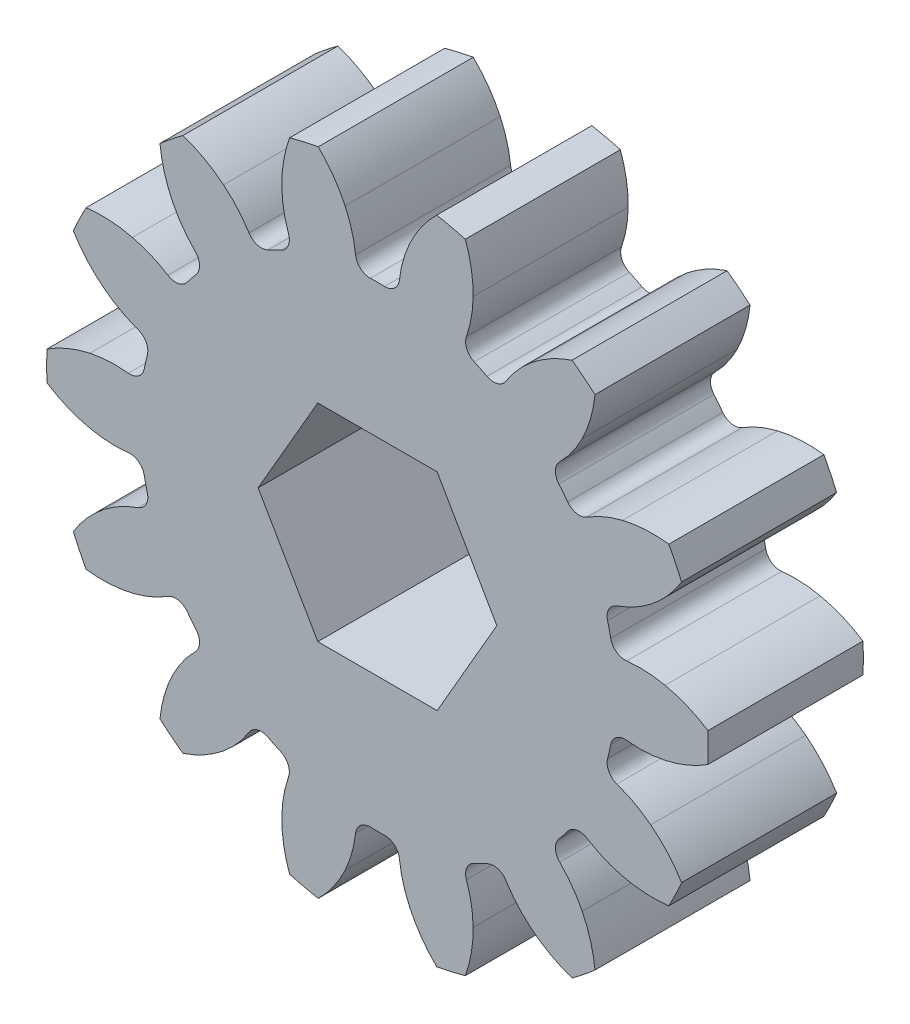
SolidWorks part; units mm, degrees
material "PLA/ABS"
ref_plane "Front" through (0, 0, 0) normal (0, 0, 1) x (1, 0, 0)
ref_plane "Top" through (0, 0, 0) normal (0, 1, 0) x (1, 0, 0)
ref_plane "Right" through (0, 0, 0) normal (1, 0, 0) x (0, 0, -1)
sketch "Sketch1" plane through (0, 0, 0) normal (0, 0, 1) x (1, 0, 0)
  line L0 (0, 0) -> (17.78, 0) construction
  line L1 (17.78, 0) -> (20.32, 0) construction
  circle A0 centre (0, 0) radius 17.78 construction
  circle A1 centre (0, 0) radius 20.32
  dimension "D1" = 35.56
  dimension "D2" = 2.54
extrude "Round Stock" add sketch "Sketch1" along normal mid plane 9.525
sketch "Sketch2" plane through (0, 0, 4.7625) normal (0, 0, 1) x (1, 0, 0)
  line L0 (0, 0) -> (14.605, 0) construction
  line L1 (14.605, 0) -> (17.78, 0) construction
  line L2 (0, 0) -> (-20.32, 0) construction
  line L3 (0, 0) -> (-18.3077, -8.8165) construction
  line L4 (-18.6809, -7.9954) -> (-16.7837, -5.8681) construction
  line L5 (-16.7837, -5.8681) -> (-13.9448, -4.3414) construction
  line L6 (-20.3, -0.9018) -> (-17.6677, -1.9952) construction
  line L7 (-17.6677, -1.9952) -> (-14.4475, -2.139) construction
  line L8 (-15.918, -7.6657) -> (-16.7837, -5.8681) construction
  line L9 (-17.6677, -1.9952) -> (-17.6677, 0) construction
  line L12 (0, 0) -> (-17.6677, -1.9952) construction
  line L13 (0, 0) -> (-16.7837, -5.8681) construction
  line L14 (-16.7837, -5.8681) -> (-13.537, -15.1543) construction
  line L15 (-17.6677, -1.9952) -> (-18.7716, 7.7801) construction
  line L16 (-16.7837, -5.8681) -> (-17.6677, -1.9952) construction
  line L17 (-14.2388, -3.2499) -> (-14.4475, -2.139) construction
  line L18 (-14.2388, -3.2499) -> (-13.9448, -4.3414) construction
  circle A0 centre (0, 0) radius 17.78 construction
  circle A1 centre (0, 0) radius 14.605 construction
  circle A2 centre (0, 0) radius 20.32 construction
  arc A3 (-18.6809, -7.9954) -> (-20.3, -0.9018) centre (0, 0) cw
  arc A4 (-13.9448, -4.3414) -> (-14.4475, -2.139) centre (0, 0) cw construction
  arc A6 (-18.6809, -7.9954) -> (-16.7837, -5.8681) centre (-11.872, -12.1583) cw
  arc A7 (-20.3, -0.9018) -> (-17.6677, -1.9952) centre (-15.9716, 5.8032) ccw
  arc A8 (-16.7837, -5.8681) -> (-14.7048, -4.7372) centre (-12.3428, -11.5554) cw
  arc A9 (-17.6677, -1.9952) -> (-15.304, -2.1121) centre (-16.1342, 5.0557) ccw
  arc A10 (-14.7048, -4.7372) -> (-14.1354, -3.6736) centre (-14.9959, -3.8972) ccw
  arc A11 (-15.304, -2.1121) -> (-14.3295, -2.8233) centre (-15.2017, -2.9952) cw
  arc A12 (-14.1354, -3.6736) -> (-14.3295, -2.8233) centre (0, 0) cw
  dimension "D6" = 35.56
  dimension "D9" = 0.889
  dimension "D12" = 7.9807
  dimension "D2" = 3.175
  dimension "D3" = 25.714
  dimension "D4" = 1.9952
  dimension "D5" = 1.9952
  dimension "D11" = 3.9726
  dimension "D8" = 20
  dimension "D7" = 20
  dimension "D14" = 9
  dimension "D15" = 9
extrude "Single Tooth" cut sketch "Sketch2" against normal through all
ref_axis "Axis" through (0, 0, 50) along (0, 0, -1)
pattern_circular "Tooth Pattern" count 14 over 360 about axis through (0, 0, 50) along (0, 0, -1) of "Single Tooth"
sketch "Sketch4" plane through (0, 0, 4.7625) normal (0, 0, 1) x (1, 0, 0)
  circle A0 centre (0, 0) radius 3.302
  dimension "D1" = 6.604
extrude "TopBearingBoss" [suppressed] add sketch "Sketch4" along normal blind 0.635
mirror "BottomBearingBoss" [suppressed] about plane through (0, 0, 0) normal (0, 0, 1)
sketch "Sketch5" plane through (0, 0, 0) normal (0, 0, 1) x (1, 0, 0)
  circle A0 centre (0, 0) radius 2.5781
  dimension "D1" = 5.1562
extrude "RoundBore" cut sketch "Sketch5" against normal through all both and the other way through all
sketch "Sketch6" [suppressed] plane through (0, 0, 0) normal (0, 0, 1) x (1, 0, 0)
  line L1 (3.6882, 6.3881) -> (-3.6882, 6.3881)
  line L2 (-3.6882, 6.3881) -> (-7.3763, 0)
  line L3 (-7.3763, 0) -> (-3.6882, -6.3881)
  line L4 (-3.6882, -6.3881) -> (3.6882, -6.3881)
  line L5 (3.6882, -6.3881) -> (7.3763, 0)
  line L6 (7.3763, 0) -> (3.6882, 6.3881)
  circle A0 centre (0, 0) radius 6.3881 construction
  circle A1 centre (0, 0) radius 6.3881 construction
extrude "Hex" [suppressed] cut sketch "Sketch6" against normal through all both and the other way through all
sketch "Sketch7" plane through (0, 0, 4.7625) normal (0, 0, 1) x (1, 0, 0)
  line L0 (-10.955, 3.556) -> (10.955, 3.556) construction
  line L1 (0, 0) -> (0, 3.556) construction
  text T0 "14" font "Adobe Gothic Std B" height 3.5
  dimension "D1" = 3.556
extrude "ToothCount" [suppressed] cut sketch "Sketch7" against normal blind 0.762
sketch "Sketch8" plane through (0, 0, -4.7625) normal (0, 0, -1) x (-1, 0, 0)
  line L1 (3.6662, -6.35) -> (7.3323, 0)
  line L2 (7.3323, 0) -> (3.6662, 6.35)
  line L3 (3.6662, 6.35) -> (-3.6662, 6.35)
  line L4 (-3.6662, 6.35) -> (-7.3323, 0)
  line L5 (-7.3323, 0) -> (-3.6662, -6.35)
  line L6 (-3.6662, -6.35) -> (3.6662, -6.35)
  circle A0 centre (0, 0) radius 6.35 construction
  dimension "D1" = 12.7
extrude "Cut-Extrude1" cut sketch "Sketch8" against normal through all
equation "\"N_teeth\"= \"No_Teeth\""
equation "\"pitch_diameter\"= \"N_teeth\" / \"Pitch\""
equation "\"Pd\"=\"N_teeth\"/\"pitch_diameter\""
equation "\"addendum\"=1.000/\"Pd\""
equation "\"face_width\"=0.375000"
equation "\"deddendum\"=1.250/\"Pd\""
equation "\"D3@Sketch2\" = 360/\"N_teeth\""
equation "\"tooth_thickness\"=1.571/\"Pd\""
equation "\"D4@Sketch2\" = \"tooth_thickness\"/2"
equation "\"D5@Sketch2\" = \"tooth_thickness\"/2"
equation "\"Pressure_Angle\"= iif ( \"Pitch\" = 20 , 14.500000 , iif ( \"Pitch\" = 32 , 20 , 20 ) )"
equation "\"base_fillet\"=0.35/\"Pd\""
equation "\"D12@Sketch2\" = 2*\"tooth_thickness\""
equation "\"hub_projection\"=0.250000"
equation "\"sss_diam\"= 0.062500"
equation "\"D1@Sketch1\"=\"pitch_diameter\""
equation "\"D2@Sketch1\"=\"addendum\""
equation "\"D1@Round Stock\" = \"face_width\""
equation "\"D2@Sketch2\"=\"deddendum\""
equation "\"D6@Sketch2\"=\"pitch_diameter\""
equation "\"D7@Sketch2\"=\"Pressure_Angle\""
equation "\"D8@Sketch2\"=\"D7@Sketch2\""
equation "\"D9@Sketch2\"=\"base_fillet\""
equation "\"D1@Tooth Pattern\" = \"N_teeth\""
equation "\"Pitch\"= \"GearPitch\""
equation "\"BossDia\"= \"BoreDia\" * 1.3"
equation "\"D1@Sketch5\"=\"BoreDia\"+\"PrintTol\""
equation "\"Hex\"= iif ( \"HexBore\" = 1 , \"unsuppressed\" , \"suppressed\" )"
equation "\"TopBearingBoss\" = iif ( \"Bearing_Boss\" = 0 , \"suppressed\" , \"unsuppressed\" )"
equation "\"BottomBearingBoss\"= iif ( \"Bearing_Boss\" > 1 , \"unsuppressed\" , \"suppressed\" )"
equation "\"D1@Sketch4\"=\"BossDia\""
equation "\"D1@Sketch7\"=\"BossDia\"/2+.01"
equation "\"ToothCount\"= iif ( \"No_Teeth\" < 22 , \"suppressed\" , \"unsuppressed\" )"
